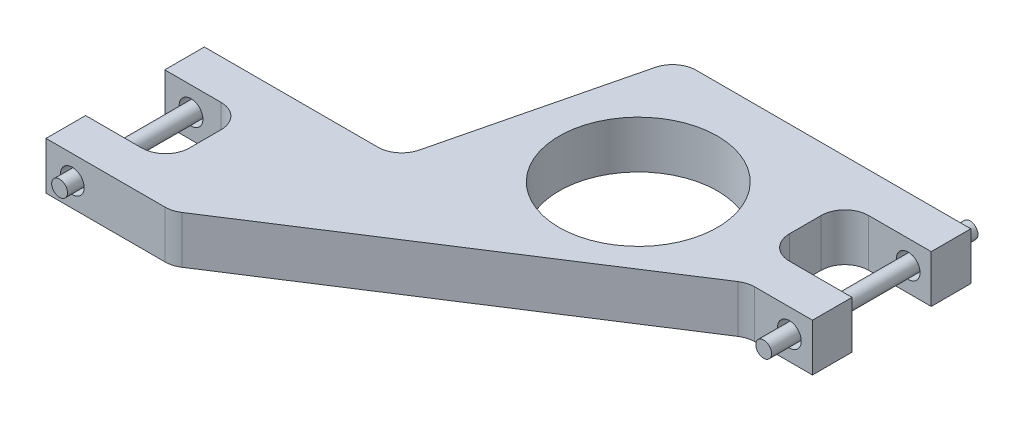
SolidWorks part; units mm, degrees
note: The reader was unsure of these and kept them because the rebuilt part matched: shared geometry of "Sketch23<3>".
ref_plane "Front Plane" through (0, 0, 0) normal (0, 0, 1) x (1, 0, 0)
ref_plane "Top Plane" through (0, 0, 0) normal (0, 1, 0) x (1, 0, 0)
ref_plane "Right Plane" through (0, 0, 0) normal (1, 0, 0) x (0, 0, -1)
sketch "Sketch21" plane through (0, 0, 0) normal (0, 1, 0) x (1, 0, 0)
  line L0 (-41.2502, -6.6917) -> (-69.1014, -6.6917)
  line L1 (-69.1014, -6.6917) -> (-69.1014, -13.0417)
  line L2 (-49.989, -32.0917) -> (-69.1014, -32.0917)
  line L3 (-69.1014, -13.0417) -> (-60.0738, -13.0417)
  line L4 (-56.2638, -16.8517) -> (-56.2638, -21.9317)
  line L5 (-60.0738, -25.7417) -> (-69.1014, -25.7417)
  line L6 (-69.1014, -25.7417) -> (-69.1014, -32.0917)
  line L7 (-64.0214, 63.5008) -> (20.6495, 63.5008) construction
  line L8 (52.8639, 77.8829) -> (52.8639, -77.8829) construction
  line L9 (8.3592, 4.1282) -> (17.631, 4.1282)
  line L10 (17.631, 4.1282) -> (17.631, 10.4782)
  line L11 (17.631, 23.1782) -> (7.5925, 23.1782)
  line L12 (3.7825, 19.3682) -> (3.7825, 14.2882)
  line L13 (7.5925, 10.4782) -> (17.631, 10.4782)
  line L14 (17.631, 29.5282) -> (-26.408, 29.5282)
  line L15 (17.631, 23.1782) -> (17.631, 29.5282)
  line L16 (-37.5494, -3.7872) -> (-30.1088, 26.6236)
  line L19 (-47.9225, -31.4826) -> (6.2927, 3.519)
  line L20 (-48.8659, -32.0917) -> (-48.8659, -6.6917) construction
  circle A0 centre (-15.5704, 9.3886) radius 12.7
  arc A1 (7.5925, 23.1782) -> (3.7825, 19.3682) centre (7.5925, 19.3682) ccw
  arc A2 (3.7825, 14.2882) -> (7.5925, 10.4782) centre (7.5925, 14.2882) ccw
  arc A3 (-60.0738, -13.0417) -> (-56.2638, -16.8517) centre (-60.0738, -16.8517) cw
  arc A4 (-56.2638, -21.9317) -> (-60.0738, -25.7417) centre (-60.0738, -21.9317) cw
  arc A5 (-30.1088, 26.6236) -> (-26.408, 29.5282) centre (-26.408, 25.7182) cw
  arc A6 (-49.989, -32.0917) -> (-47.9225, -31.4826) centre (-49.989, -28.2817) ccw
  arc A7 (-37.5494, -3.7872) -> (-41.2502, -6.6917) centre (-41.2502, -2.8817) cw
  arc A8 (8.3592, 4.1282) -> (6.2927, 3.519) centre (8.3592, 0.3182) ccw
  dimension "D9" = 25.4
  dimension "D7" = 3.81
  dimension "D8" = 3.81
  dimension "D1" = 84.6709
  dimension "D2" = 4.1282
  dimension "D3" = 5.08
  dimension "D4" = 25.4
  dimension "D5" = 6.35
  dimension "D6" = 25.4
extrude "Extrude1" add sketch "Sketch21" along normal mid plane 7.62
sketch "Sketch22" plane through (0, 0, -29.5282) normal (0, 0, -1) x (-1, 0, 0)
  line L0 (-17.631, 0) -> (77.4589, 0) construction
  circle A0 centre (-13.9288, 0) radius 1.905
  circle A1 centre (64.8874, 0.0093) radius 1.905
  dimension "D1" = 78.8162
  dimension "D3" = 3.81
extrude "Cut-Extrude1" cut sketch "Sketch22" against normal mid plane 183.515
sketch "Sketch23" plane through (0, 0, 0) normal (0, 0, 1) x (1, 0, 0)
  circle A0 centre (-64.8874, 0.0093) radius 1.27
  circle A1 centre (13.9288, 0) radius 1.27
  dimension "D1" = 2.54
extrude "Extrude2" add sketch "Sketch23" against normal blind 33.114 separate body contours A1
extrude "Extrude3" add sketch "Sketch23<3>" along normal blind 29.05 from offset 5.08 separate body contours A0
sketch "Sketch23<3>" plane through (0, 0, 0) normal (0, 0, 1) x (1, 0, 0) same geometry as "Sketch23"
